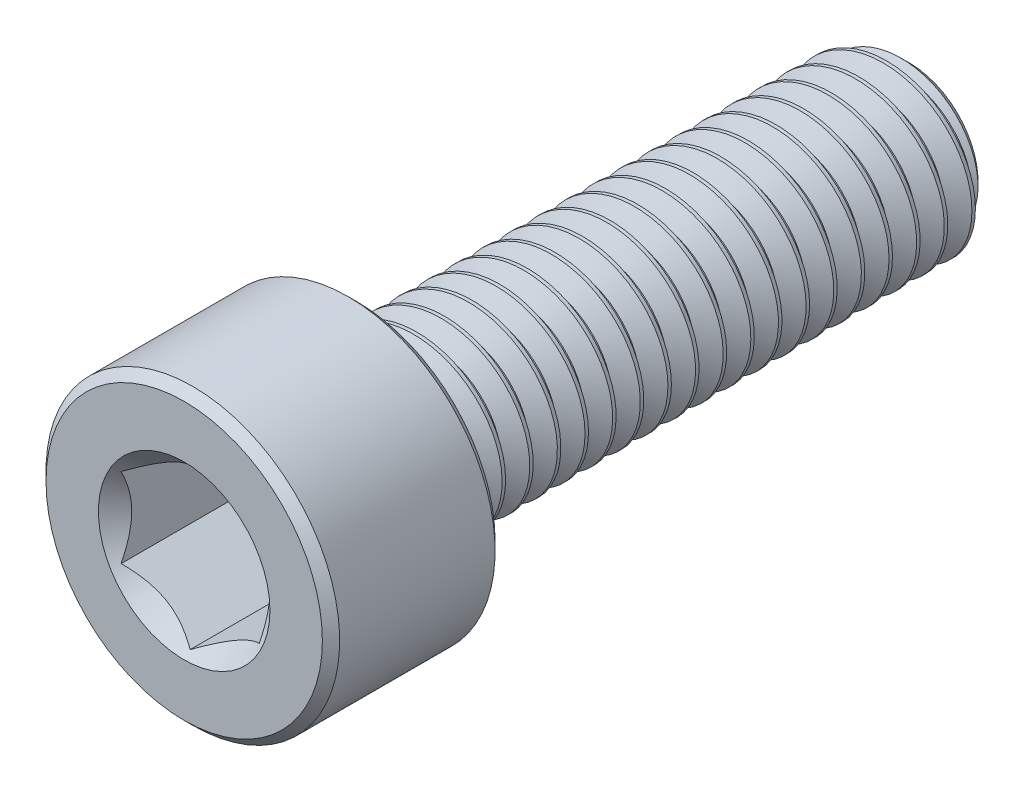
SolidWorks part; units mm, degrees
ref_plane "Front Plane" through (0, 0, 0) normal (0, 0, 1) x (1, 0, 0)
ref_plane "Top Plane" through (0, 0, 0) normal (0, 1, 0) x (1, 0, 0)
ref_plane "Right Plane" through (0, 0, 0) normal (1, 0, 0) x (0, 0, -1)
sketch "Sketch1" plane through (0, 0, 0) normal (1, 0, 0) x (0, 0, -1)
  line L0 (-10.5, 0) -> (10.5, 0) construction
  line L1 (10.5, 0) -> (10.5, 1.9804) construction
  line L2 (10.5, 1.9804) -> (9.9804, 2.5) construction
  line L3 (9.9804, 2.5) -> (9.9, 2.5) construction
  line L4 (9.9, 2.5) -> (-5.5, 2.5) construction
  line L5 (-5.5, 2.5) -> (-5.5, 4.25) construction
  line L6 (-5.5, 4.25) -> (-10.5, 4.25) construction
  line L7 (-10.5, 4.25) -> (-10.5, 0) construction
  line L8 (10.5, 1.9804) -> (10.5, 2.5) construction
  line L9 (10.45, 2.5866) -> (10.85, 1.8938) construction
  line L10 (10.85, 1.8938) -> (11.25, 2.5866) construction
  line L11 (11.25, 2.5866) -> (10.45, 2.5866) construction
  line L12 (10.85, 2.5866) -> (10.85, 2.5) construction
  line L13 (10.85, 1.8938) -> (10.85, 1.9804) construction
  line L14 (10.8, 1.9804) -> (10.9, 1.9804) construction
  line L15 (10.5, 2.5) -> (11.2, 2.5) construction
  line L16 (10.475, 2.5433) -> (11.225, 2.5433) construction
  line L17 (10.5, 0) -> (10.5, -2.5) construction
  line L18 (-5.75, 4.25) -> (-5.5, 4) construction
  line L19 (-10.25, 4.25) -> (-10.5, 4) construction
  line L20 (-5.5, 2.5) -> (-5.5, 0) construction
  line L21 (-5.5, 1.25) -> (-0.1667, 1.25) construction
  line L22 (-0.1667, 1.25) -> (5.1667, 1.25) construction
  line L23 (5.1667, 1.25) -> (10.5, 1.25) construction
  line L24 (-0.1667, 1.25) -> (-0.1667, 2.5) construction
  line L25 (-0.1667, 2.5) -> (-0.1667, 4.25) construction
  line L26 (5.1667, 1.25) -> (5.1667, 4.25) construction
  point P0 (-10.5, 2)
  point P3 (8.5, 2.5)
  point P4 (0, 0)
  point P18 (5.1667, 2.5)
  point P22 (10.85, 1.9804)
  point P24 (9.9, 2.5)
  point P25 (10.85, 2.5)
  point P28 (10.85, 2.5433)
  point P29 (8.5, -2.5)
  point P30 (-0.1667, 2.5)
  point P31 (-8, 4.25)
  point P37 (-6.375, 4.25)
  point P38 (-10.125, 4.25)
  point P45 (-0.1667, 1.25)
  point P46 (5.1667, 1.25)
  dimension "D2" = 0.1
  dimension "D7" = 0.25
  dimension "D8" = 0.25
  dimension "D9" = 0.25
  dimension "D10" = 0.125
  dimension "D11" = 0.625
  dimension "Drive Size" = 4
  dimension "Head Diameter" = 8.5
  dimension "Head Height" = 5
  dimension "Thread Pitch" = 0.8
  dimension "Thread Dia" = 5
  dimension "Length" = 16
  dimension "D12" = 0.6
  dimension "D4" = 2
  dimension "D3" = 45
sketch "Sketch2" plane through (0, 0, 0) normal (1, 0, 0) x (0, 0, -1)
  line L0 (-10.5, 0) -> (-10.5, 4)
  line L1 (-10.25, 4.25) -> (-5.75, 4.25)
  line L2 (-5.5, 4) -> (-5.5, 2.75)
  line L4 (9.9804, 2.5) -> (10.5, 1.9804)
  line L5 (10.5, 1.9804) -> (10.5, 0)
  line L6 (-5.5, 4.25) -> (-10.5, 4.25) construction
  line L7 (10.5, 0) -> (-10.5, 0)
  line L8 (-10.25, 4.25) -> (-10.5, 4) construction
  line L10 (-10.25, 4.25) -> (-10.5, 4)
  line L14 (-5.75, 4.25) -> (-5.5, 4) construction
  line L16 (-5.75, 4.25) -> (-5.5, 4)
  line L17 (-5.5, 2.5) -> (-5.5, 4.25) construction
  line L19 (-5.25, 2.5) -> (9.9804, 2.5)
  line L20 (9.9, 2.5) -> (-5.5, 2.5) construction
  arc A1 (-5.5, 2.75) -> (-5.25, 2.5) centre (-5.25, 2.75) ccw
  dimension "D3" = 0.25
revolve "Revolve1" add sketch "Sketch2" angle 360 about L7
sketch "Sketch3" plane through (0, 0, 10.5) normal (0, 0, 1) x (1, 0, 0)
  line L1 (2, -1.1547) -> (2, 1.1547)
  line L2 (2, 1.1547) -> (0, 2.3094)
  line L3 (0, 2.3094) -> (-2, 1.1547)
  line L4 (-2, 1.1547) -> (-2, -1.1547)
  line L5 (-2, -1.1547) -> (0, -2.3094)
  line L6 (0, -2.3094) -> (2, -1.1547)
  circle A0 centre (0, 0) radius 2 construction
  circle A1 centre (0, 0) radius 4.25 construction
  circle A2 centre (0, 0) radius 4.25 construction
  circle A3 centre (0, 0) radius 2.3094 construction
  point P13 (0, 0)
  dimension "D1" = 4.6188
extrude "Cut-Extrude1" cut sketch "Sketch3" against normal offset from surface (4 mm away) 1 up to face at (0, 4, 5.5)
sketch "Sketch4" plane through (0, 0, 10.5) normal (0, 0, 1) x (1, 0, 0)
  circle A0 centre (0, 0) radius 2.4826
  dimension "D1" = 4.9652
extrude "Cut-Extrude2" cut sketch "Sketch4" against normal up to vertex (2.5 mm away) draft 45 up to point (0, 4.25, 8)
sketch "Sketch11" plane through (0, 0, 0) normal (1, 0, 0) x (0, 0, -1)
  line L0 (-10.5, 0) -> (10.5, 0) construction
  line L1 (-10.5, 0) -> (10.5, 0) construction
  line L2 (-2.5, 0) -> (-2.5, 2.5) construction
  line L3 (9.9, 2.5) -> (-5.5, 2.5) construction
  line L4 (7.5, 0) -> (7.5, 2.5) construction
  line L6 (10.5, 1.9804) -> (10.5, 2.5) construction
  point P2 (-2.5, 0)
  point P3 (7.5, 0)
  dimension "D1" = 3
  dimension "D2" = 3
sketch "Sketch6" plane through (0, 0, -10.5) normal (0, 0, -1) x (-1, 0, 0)
  circle A0 centre (0, 0) radius 2.5
curve "Helix/Spiral1" pitch 0.8 height 16.8 turns 21
sketch "Sketch10" plane through (0, 0, 0) normal (1, 0, 0) x (0, 0, -1)
  line L0 (-5.25, -4.25) -> (-5.25, 4.25)
  line L5 (-10.5, 0) -> (10.5, 0) construction
  line L6 (-5.25, 2.5) -> (-5.25, -2.5) construction
  point P3 (-5.25, 0)
split "Split1" trim tools "Sketch10" bodies to split 106 resulting bodies 114 115
sketch "Sketch7" plane through (0, 0, 0) normal (1, 0, 0) x (0, 0, -1)
  line L0 (10.475, 2.5433) -> (11.225, 2.5433)
  line L1 (11.225, 2.5433) -> (10.9, 1.9804)
  line L2 (10.9, 1.9804) -> (10.8, 1.9804)
  line L3 (10.8, 1.9804) -> (10.475, 2.5433)
sweep "Cut-Sweep1" cut profiles "Sketch7" path "Helix/Spiral1" align with end faces yes
sketch "Sketch8" plane through (0, 0, 0) normal (1, 0, 0) x (0, 0, -1)
  line L0 (-5.5, 0) -> (-5.5, 2.5)
  line L1 (-5.25, -2.5) -> (-5.25, 2.5) construction
  line L2 (-5.5, 2.5) -> (-5.25, 2.5)
  line L4 (-5.25, 2.5) -> (-3.8066, 0)
  line L5 (-3.8066, 0) -> (-5.5, 0)
  line L6 (9.9, 2.5) -> (-5.5, 2.5) construction
  line L7 (-10.5, 0) -> (10.5, 0) construction
  dimension "D1" = 60
revolve "Revolve2" add sketch "Sketch8" angle 360 about L5
equation "\"D2@Sketch1\" = \"Thread Pitch@Sketch1\" / 8"
equation "\"D4@Helix/Spiral1\" = \"Thread Pitch@Sketch1\""
equation "\"D7@Sketch1\" = \"Head Height@Sketch1\" * .05"
equation "\"D8@Sketch1\"=\"D7@Sketch1\""
equation "\"D9@Sketch1\"=\"D7@Sketch1\""
equation "\"D10@Sketch1\"=\"D7@Sketch1\"/2"
equation "\"D11@Sketch1\"=\"D10@Sketch1\"*5"
equation "\"D4@Sketch1\"=\"Thread Pitch@Sketch1\"*2.5"
equation "\"D12@Sketch1\"=\"Thread Pitch@Sketch1\"*.75"
equation "\"D3@Helix/Spiral1\"=\"Length@Sketch1\"+\"Thread Pitch@Sketch1\""
equation "\"D3@Sketch2\"=\"Thread Dia@Sketch1\"*0.05"
equation "\"D1@Sketch11\"=\"Length@Sketch1\"*0.1875"
equation "\"D2@Sketch11\"=\"D1@Sketch11\""
equation "\"D1@Sketch4\"=\"D1@Sketch3\"*1.075"
